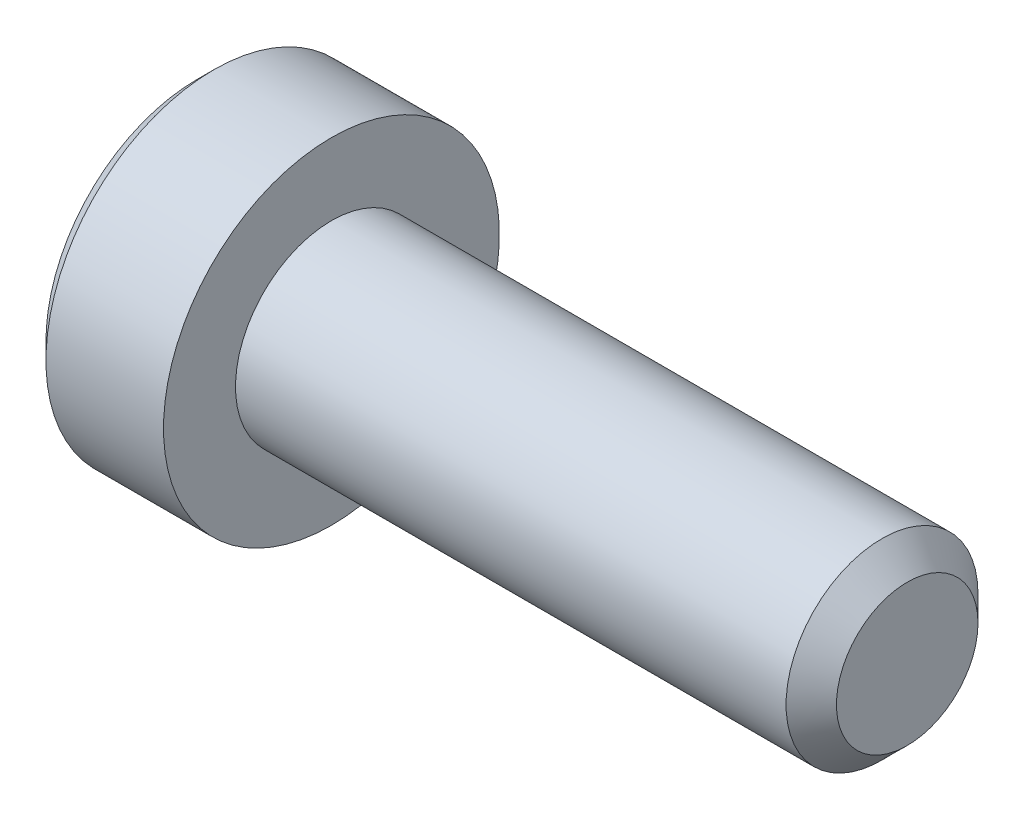
SolidWorks part; units mm, degrees
material "Alloy Steel"
ref_plane "Front Plane" through (0, 0, 0) normal (0, 0, 1) x (1, 0, 0)
ref_plane "Top Plane" through (0, 0, 0) normal (0, 1, 0) x (1, 0, 0)
ref_plane "Right Plane" through (0, 0, 0) normal (1, 0, 0) x (0, 0, -1)
sketch "Sketch1" plane through (0, 0, 0) normal (0, 0, 1) x (1, 0, 0)
  line L0 (6, 0) -> (-6, 0) construction
  line L1 (6, 2) -> (6, -2) construction
  line L2 (-6, 3.5) -> (-6, -3.5) construction
  line L3 (-6, 3.5) -> (-8.45, 3.5) construction
  line L4 (-8.45, 3.5) -> (-8.8, 3.15) construction
  line L5 (-8.8, 3.15) -> (-8.8, -3.15) construction
  line L6 (-8.8, -3.15) -> (-8.45, -3.5) construction
  line L7 (-8.45, -3.5) -> (-6, -3.5) construction
  point P7 (-6.38, 0)
  point P12 (3.2, -2)
  dimension "D1" = 45
  dimension "Dec." = 4
  dimension "Length" = 12
  dimension "Head Dia" = 7
  dimension "Head Height" = 2.8
  dimension "Hex Depth" = 2.42
  dimension "Chamfer" = 0.35
  dimension "D2" = 2.8
ref_plane "Plane1" through (6, 0, 0) normal (1, 0, 0) x (0, 0, -1)
ref_plane "Plane2" through (-8.8, 0, 0) normal (1, 0, 0) x (0, 0, -1)
sketch "Sketch2" plane through (6, 0, 0) normal (1, 0, 0) x (0, 0, -1)
  circle A0 centre (0, 0) radius 2
extrude "Boss-Extrude1" add sketch "Sketch2" against normal up to vertex (12 mm away) up to point (-6, 0, 0)
sketch "Sketch3" plane through (6, 0, 0) normal (1, 0, 0) x (0, 0, -1)
  circle A0 centre (0, 0) radius 2 construction
  circle A1 centre (0, 0) radius 2
curve "Helix/Spiral1" pitch 0.7 height 12.67 turns 18.1 parameters "Pitch"=0.7
chamfer "Chamfer1" distance 0.525 angle 45 1 edges at (6, 0, -2)
sketch "Sketch5" plane through (0, 0, 0) normal (0, 0, 1) x (1, 0, 0)
  line L0 (6, 2) -> (6.6125, 2)
  line L1 (6.6125, 2) -> (6.35, 1.5453)
  line L2 (6.35, 1.5453) -> (6.2625, 1.5453)
  line L3 (6.2625, 1.5453) -> (6, 2)
  line L4 (6.3063, 1.5453) -> (6.3063, 2) construction
  line L5 (6.1313, 1.7727) -> (6.4813, 1.7727) construction
  dimension "D1" = 60
  dimension "D2" = 0.35
  dimension "D3" = 0.0875
sweep "Cut-Sweep1" [suppressed] cut profiles "Sketch5" path "Helix/Spiral1"
sketch "Sketch4" plane through (-8.8, 0, 0) normal (1, 0, 0) x (0, 0, -1)
  line L0 (-3.5, 0.7937) -> (3.5, 0.7937) construction
  line L1 (0, 1.4434) -> (-1.25, 0.7217)
  line L2 (-1.25, 0.7217) -> (-1.25, -0.7217)
  line L3 (-1.25, -0.7217) -> (0, -1.4434)
  line L4 (0, -1.4434) -> (1.25, -0.7217)
  line L5 (1.25, -0.7217) -> (1.25, 0.7217)
  line L6 (1.25, 0.7217) -> (0, 1.4434)
  line L7 (0, 0) -> (0, 0.7937) construction
  circle A0 centre (0, 0) radius 1.25 construction
  dimension "Hex Size" = 2.5
  dimension "D1" = 7
  dimension "D2" = 0.7937
sketch "Sketch6" plane through (0, 0, 0) normal (0, 0, 1) x (1, 0, 0)
  line L0 (-8.45, 3.5) -> (-8.8, 3.15) construction
  line L1 (-6, 3.5) -> (-8.45, 3.5) construction
  line L2 (-6, 3.5) -> (-6, -3.5) construction
  line L3 (-8.8, 3.15) -> (-8.8, -3.15) construction
  line L4 (-8.45, 3.5) -> (-8.8, 3.15)
  line L5 (-6, 3.5) -> (-8.45, 3.5)
  line L6 (-6, 3.5) -> (-6, 0)
  line L7 (-8.8, 3.15) -> (-8.8, 0)
  line L8 (-6, 0) -> (-8.8, 0) construction
  line L9 (-6, 0) -> (-8.8, 0)
revolve "Revolve1" add sketch "Sketch6" angle 360 about L8
extrude "Cut-Extrude1" cut sketch "Sketch4" along normal up to vertex (2.42 mm away) up to point (-6.38, 0, 0)
sketch "Sketch8" plane through (-8.8, 0, 0) normal (-1, 0, 0) x (0, 0, 1)
  circle A1 centre (0, 0) radius 1.4434
extrude "Cut-Extrude2" cut sketch "Sketch8" against normal through all draft 45
equation "\"D3@Helix/Spiral1\" = \"Length@Sketch1\"+\"Pitch@Helix/Spiral1\"-.03"
equation "\"D3@Sketch5\" = \"Pitch@Helix/Spiral1\"*.125"
equation "\"D2@Sketch5\" = \"Pitch@Helix/Spiral1\"*.50"
equation "\"D1@Chamfer1\" = \"Pitch@Helix/Spiral1\"*.75"
equation "\"D2@Sketch1\" = \"Pitch@Helix/Spiral1\"*4"
equation "\"D1@Sketch4\" = \"Head Dia@Sketch1\""
equation "\"Chamfer@Sketch1\" = \"Head Height@Sketch1\"/8"
